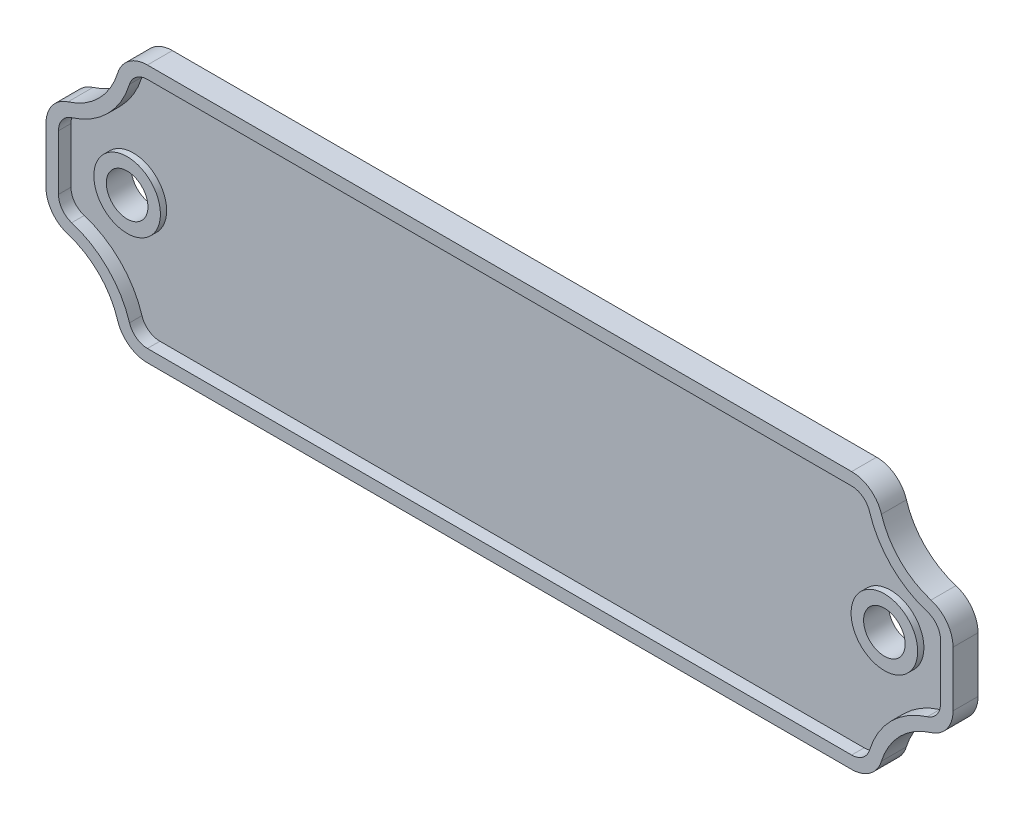
SolidWorks part; units mm, degrees
ref_plane "Front Plane" through (0, 0, 0) normal (0, 0, 1) x (1, 0, 0)
ref_plane "Top Plane" through (0, 0, 0) normal (0, 1, 0) x (1, 0, 0)
ref_plane "Right Plane" through (0, 0, 0) normal (1, 0, 0) x (0, 0, -1)
sketch "Sketch2" plane through (0, 0, 0) normal (0, 0, 1) x (1, 0, 0)
  line L0 (-42.3139, 14) -> (42.3139, 14)
  line L1 (0, -15.5) -> (42.3139, -15.5)
  line L2 (-54.5, -3.3139) -> (-54.5, 3.3139)
  line L4 (54.5, -3.3139) -> (54.5, 3.3139)
  line L5 (53, -3.3139) -> (53, 3.3139)
  line L6 (-42.3139, -14) -> (42.3139, -14)
  line L7 (-53, -3.3139) -> (-53, 3.3139)
  line L8 (-54.5, -3.3139) -> (-54.5, 3.3139)
  line L11 (-42.3139, 15.5) -> (42.3139, 15.5)
  line L12 (-42.3139, -15.5) -> (42.3139, -15.5)
  circle A0 centre (-45.5, 0) radius 2.5
  circle A1 centre (-45.5, 0) radius 4
  arc A2 (-51.8529, 6.8981) -> (-45.8981, 12.8529) centre (-54.5, 15.5) ccw
  arc A3 (-54.5, 3.3139) -> (-51.8529, 6.8981) centre (-50.75, 3.3139) cw
  arc A4 (-42.3139, 15.5) -> (-45.8981, 12.8529) centre (-42.3139, 11.75) ccw
  arc A5 (-54.5, -3.3139) -> (-51.8529, -6.8981) centre (-50.75, -3.3139) ccw
  arc A6 (-51.8529, -6.8981) -> (-45.8981, -12.8529) centre (-54.5, -15.5) cw
  arc A7 (-42.3139, -15.5) -> (-45.8981, -12.8529) centre (-42.3139, -11.75) cw
  arc A8 (54.5, 3.3139) -> (51.8529, 6.8981) centre (50.75, 3.3139) ccw
  arc A9 (51.8529, 6.8981) -> (45.8981, 12.8529) centre (54.5, 15.5) cw
  arc A10 (42.3139, -15.5) -> (45.8981, -12.8529) centre (42.3139, -11.75) ccw
  arc A11 (51.8529, -6.8981) -> (45.8981, -12.8529) centre (54.5, -15.5) ccw
  arc A12 (54.5, -3.3139) -> (51.8529, -6.8981) centre (50.75, -3.3139) cw
  arc A13 (42.3139, 15.5) -> (45.8981, 12.8529) centre (42.3139, 11.75) cw
  circle A14 centre (45.5, 0) radius 2.5
  circle A15 centre (45.5, 0) radius 4
  arc A16 (-53, 3.3139) -> (-51.4118, 5.4644) centre (-50.75, 3.3139) cw
  arc A17 (-51.4118, 5.4644) -> (-44.4644, 12.4118) centre (-54.5, 15.5) ccw
  arc A18 (-42.3139, 14) -> (-44.4644, 12.4118) centre (-42.3139, 11.75) ccw
  arc A19 (42.3139, 14) -> (44.4644, 12.4118) centre (42.3139, 11.75) cw
  arc A20 (51.4118, 5.4644) -> (44.4644, 12.4118) centre (54.5, 15.5) cw
  arc A21 (53, 3.3139) -> (51.4118, 5.4644) centre (50.75, 3.3139) ccw
  arc A22 (53, -3.3139) -> (51.4118, -5.4644) centre (50.75, -3.3139) cw
  arc A23 (51.4118, -5.4644) -> (44.4644, -12.4118) centre (54.5, -15.5) ccw
  arc A24 (42.3139, -14) -> (44.4644, -12.4118) centre (42.3139, -11.75) ccw
  arc A25 (-53, -3.3139) -> (-51.4118, -5.4644) centre (-50.75, -3.3139) ccw
  arc A26 (-51.4118, -5.4644) -> (-44.4644, -12.4118) centre (-54.5, -15.5) cw
  arc A27 (-42.3139, -14) -> (-44.4644, -12.4118) centre (-42.3139, -11.75) cw
  point P0 (0, 0)
  dimension "D3" = 9
  dimension "D4" = 9
  dimension "D5" = 3.75
  dimension "D6" = 1.5
  dimension "D1" = 109
  dimension "D2" = 31
  dimension "D7" = 1.5
  dimension "D8" = 1.5
extrude "Boss-Extrude1" add sketch "Sketch2" along normal blind 1.5 contours A27 L6 A24 A23 A22 L5 A21 A20 A19 L0 A18 A17 A16 L7 A25 A26 A1 A15 region at (0, 0, 0)
extrude "Boss-Extrude2" add sketch "Sketch2<3>" along normal blind 3 contours A13 L11 A4 A2 A3 L2 A5 A6 A7 L12 L1 A10 A11 A12 L4 A8 A9 L6 A27 A26 A25 L7 A16 A17 A18 L0 A19 A20 A21 L5 A22 A23 A24 region at (-21.157, -14.3668, 0)
sketch "Sketch2<3>" plane through (0, 0, 0) normal (0, 0, 1) x (1, 0, 0) same geometry as "Sketch2"
extrude "Boss-Extrude3" add sketch "Sketch2<4>" along normal blind 2.25 contours A15 A14 | A1 A0 region at (-49.3869, 0, 0) region at (41.6131, 0, 0)
sketch "Sketch2<4>" plane through (0, 0, 0) normal (0, 0, 1) x (1, 0, 0) same geometry as "Sketch2"
extrude "Boss-Extrude4" add sketch "Sketch2<5>" against normal blind 0.75 contours A15 A14 | A1 A0 region at (-49.3869, 0, 0) region at (41.6131, 0, 0)
sketch "Sketch2<5>" plane through (0, 0, 0) normal (0, 0, 1) x (1, 0, 0) same geometry as "Sketch2"
